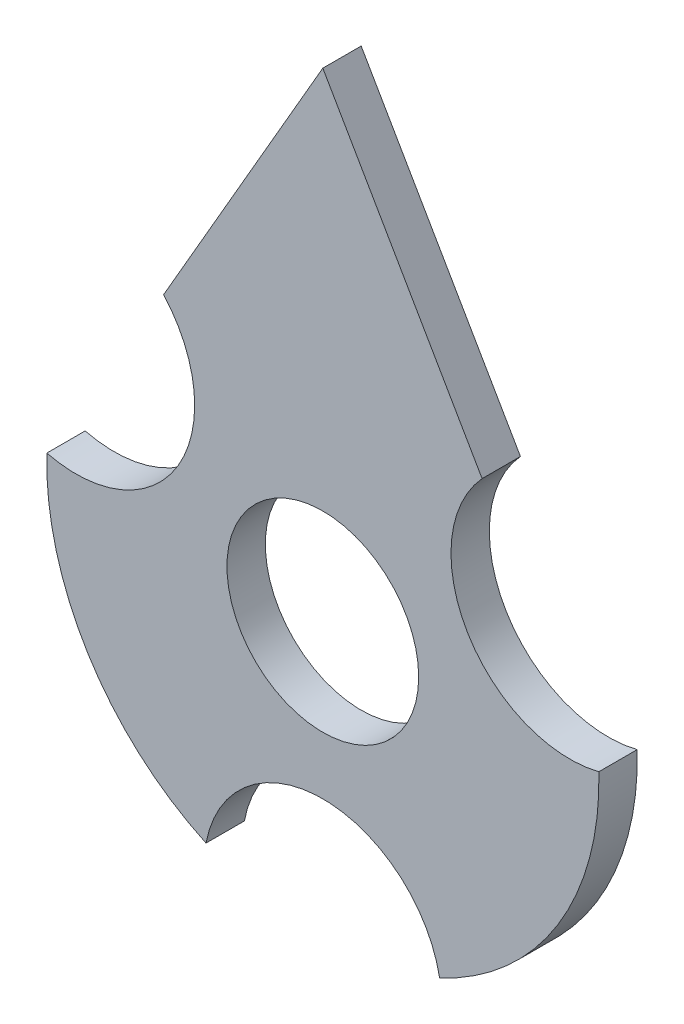
SolidWorks part; units mm, degrees
ref_plane "Front Plane" through (0, 0, 0) normal (0, 0, 1) x (1, 0, 0)
ref_plane "Top Plane" through (0, 0, 0) normal (0, 1, 0) x (1, 0, 0)
ref_plane "Right Plane" through (0, 0, 0) normal (1, 0, 0) x (0, 0, -1)
sketch "Sketch1" plane through (0, 0, 0) normal (0, 0, 1) x (1, 0, 0)
  line L0 (0, 125) -> (-41.5302, 53.0676)
  line L1 (0, 125) -> (41.5302, 53.0676)
  line L2 (0, 0) -> (0, 85.421) construction
  circle A0 centre (0, 0) radius 25
  arc A1 (-71.9696, 2.0937) -> (-41.5302, 53.0676) centre (-64.4184, 32.16) ccw
  arc A2 (30.4601, -65.2394) -> (-30.4601, -65.2394) centre (0, -71) ccw
  arc A4 (71.9696, 2.0937) -> (41.5302, 53.0676) centre (64.4184, 32.16) cw
  arc A5 (-71.9696, 2.0937) -> (-30.4601, -65.2394) centre (0, 0) ccw
  arc A6 (30.4601, -65.2394) -> (71.9696, 2.0937) centre (0, 0) ccw
  point P9 (0, 0)
  point P11 (0, 0)
  point P13 (0, 0)
  point P15 (0, 0)
  point P16 (41.5302, 53.0676)
  point P17 (0, 0)
  point P18 (0, 0)
  point P22 (0, 0)
  dimension "D1" = 50
  dimension "D4" = 62
  dimension "D7" = 62
  dimension "D9" = 72
  dimension "D2" = 60
  dimension "D3" = 30
  dimension "D5" = 113
  dimension "D6" = 125
  dimension "D8" = 196
extrude "Boss-Extrude1" add sketch "Sketch1" along normal mid plane 10
